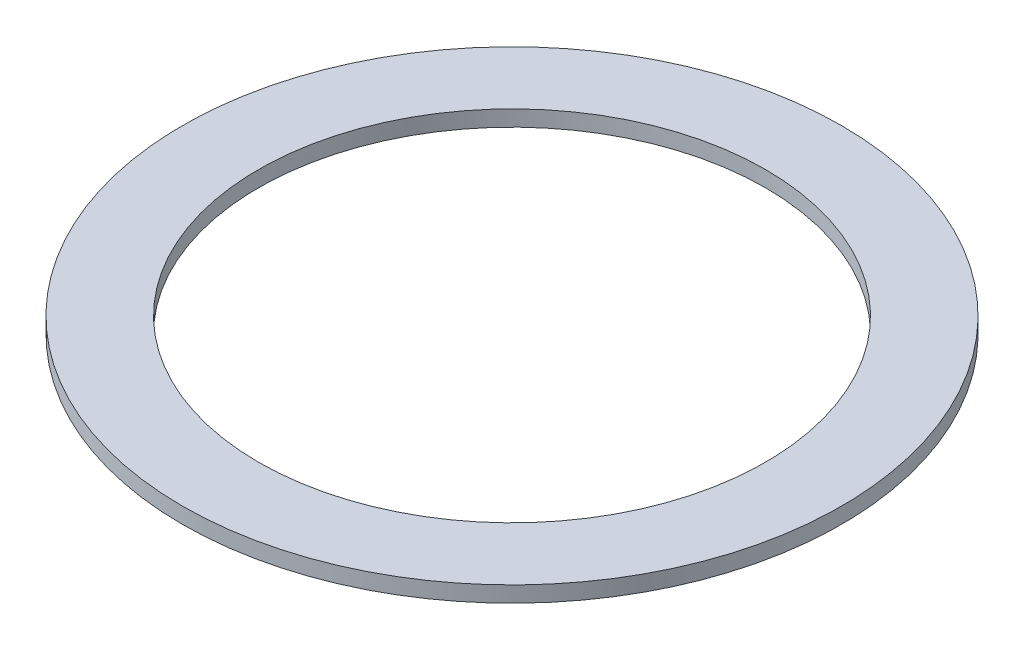
SolidWorks part; units mm, degrees
ref_plane "Front Plane" through (0, 0, 0) normal (0, 0, 1) x (1, 0, 0)
ref_plane "Top Plane" through (0, 0, 0) normal (0, 1, 0) x (1, 0, 0)
ref_plane "Right Plane" through (0, 0, 0) normal (1, 0, 0) x (0, 0, -1)
sketch "Sketch1" plane through (0, 0, 0) normal (0, 1, 0) x (1, 0, 0)
  circle A0 centre (0, 0) radius 25.4
  circle A1 centre (0, 0) radius 33.02
  dimension "D1" = 50.8
  dimension "D2" = 66.04
extrude "Boss-Extrude1" add sketch "Sketch1" along normal blind 1.5875
equation "\"D1@Sketch1\"=2in"
equation "\"D2@Sketch1\"=2.6in"
